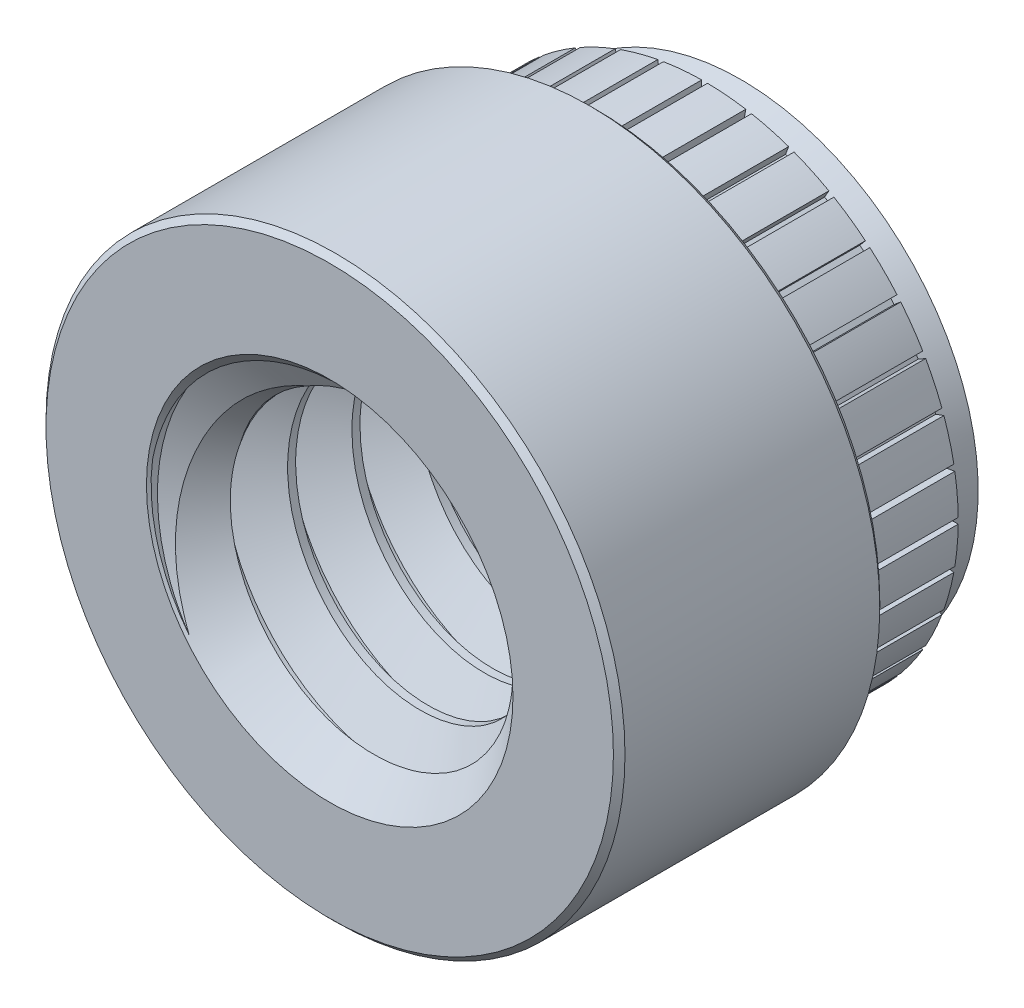
SolidWorks part; units mm, degrees
ref_plane "Front Plane" through (0, 0, 0) normal (0, 0, 1) x (1, 0, 0)
ref_plane "Top Plane" through (0, 0, 0) normal (0, 1, 0) x (1, 0, 0)
ref_plane "Right Plane" through (0, 0, 0) normal (1, 0, 0) x (0, 0, -1)
sketch "Sketch1" plane through (0, 0, 0) normal (0, 0, 1) x (1, 0, 0)
  circle A0 centre (0, 0) radius 6.35
  dimension "A" = 12.7
extrude "Extrude1" add sketch "Sketch1" against normal blind 5.842
sketch "Sketch15" plane through (0, 0, -5.842) normal (0, 0, -1) x (-1, 0, 0)
  circle A0 centre (0, 0) radius 5.2451
  dimension "hole dia" = 10.4902
sketch "Sketch2" plane through (0, 0, -5.842) normal (0, 0, -1) x (-1, 0, 0)
  circle A0 centre (0, 0) radius 5.5626
  dimension "D1" = 11.1252
extrude "Extrude2" add sketch "Sketch2" along normal blind 3.175
sketch "Sketch3" plane through (0, 0, -9.017) normal (0, 0, -1) x (-1, 0, 0)
  line L0 (0, 5.3721) -> (0, 6.35)
  circle A1 centre (0, 0) radius 6.35 construction
  circle A2 centre (0, 0) radius 5.3721
  circle A3 centre (0, 0) radius 5.3721 construction
  dimension "D1" = 0.1905
extrude "Cut-Extrude-Thin1" cut sketch "Sketch3" against normal up to surface (3.175 mm away) thin up to face at (6.35, 0, -5.842) thin type mid plane wall 0.127
pattern_circular "CirPattern1" count 36 over 360 about axis through (0, 0, 0) along (0, 0, 1) of "Cut-Extrude-Thin1"
sketch "Sketch5" plane through (0, 0, -9.017) normal (0, 0, -1) x (-1, 0, 0)
  circle A0 centre (0, 0) radius 6.35 construction
  circle A3 centre (0, 0) radius 5.207
  dimension "C" = 10.414
extrude "Cut-Extrude1" cut sketch "Sketch5" against normal blind 0.7937 draft 20 flip side to cut draft outward yes
chamfer "Chamfer2" distance 0.127 angle 45 2 edges at (6.35, 0, 0) (6.35, 0, -5.842)
sketch "Sketch7" plane through (0, 0, 0) normal (0, 0, 1) x (1, 0, 0)
  circle A0 centre (0, 0) radius 3.9688
  dimension "Thread Od" = 7.9375
extrude "Cut-Extrude3" cut sketch "Sketch7" against normal through all
sketch "Sketch8" plane through (0, 0, -9.017) normal (0, 0, -1) x (-1, 0, 0)
  circle A0 centre (0, 0) radius 3.9688 construction
  circle A1 centre (0, 0) radius 3.9688
curve "Helix/Spiral1" pitch 1.4111 height 12.192 turns 8.64 parameters "pitch"=1.4111
sketch "Sketch9" plane through (0, 0, 0) normal (1, 0, 0) x (0, 0, -1)
  line L0 (10.2517, 3.9688) -> (9.7226, 3.0522)
  line L1 (9.7226, 3.0522) -> (9.5462, 3.0522)
  line L2 (9.5462, 3.0522) -> (9.017, 3.9688)
  line L3 (10.2517, 3.9688) -> (9.017, 3.9688)
  line L4 (9.6344, 3.9688) -> (9.6344, 3.0522) construction
  line L5 (9.9871, 3.5105) -> (9.2816, 3.5105) construction
  line L6 (9.017, -3.9688) -> (9.017, 3.9688) construction
  dimension "D1" = 60
  dimension "D2" = 0.1764
  dimension "D3" = 0.7056
sweep "Sweep1" add profiles "Sketch9" path "Helix/Spiral1"
sketch "Sketch10" plane through (0, 0, 0) normal (0, 0, 1) x (1, 0, 0)
  circle A0 centre (0, 0) radius 6.35 construction
  circle A1 centre (0, 0) radius 6.35
extrude "Cut-Extrude4" cut sketch "Sketch10" along normal through all
sketch "Sketch11" plane through (0, 0, -9.017) normal (0, 0, -1) x (-1, 0, 0)
  circle A1 centre (0, 0) radius 5.207 construction
  circle A2 centre (0, 0) radius 5.207
extrude "Cut-Extrude5" cut sketch "Sketch11" along normal through all
sketch "Sketch13" plane through (0, 0, 0) normal (0, 0, 1) x (1, 0, 0)
  circle A2 centre (0, 0) radius 4.0196
  circle A3 centre (0, 0) radius 4.0196
  dimension "D1" = 0.0508
extrude "Cut-Extrude6" cut sketch "Sketch13" against normal through all draft 45
sketch "Sketch14" plane through (0, 0, -9.017) normal (0, 0, -1) x (-1, 0, 0)
  circle A2 centre (0, 0) radius 4.0196
  circle A3 centre (0, 0) radius 4.0196
  dimension "D1" = 0.0508
extrude "Cut-Extrude7" cut sketch "Sketch14" against normal through all draft 45
equation "\"D3@Helix/Spiral1\" = \"B@Extrude1\"+\"panel min.@Extrude2\"+.125"
equation "\"D2@Sketch9\" = \"pitch@Helix/Spiral1\"*.125"
equation "\"D3@Sketch9\" = \"pitch@Helix/Spiral1\"*.50"
equation "\"D1@Sketch2\" = \"hole dia@Sketch15\"+.025"
equation "\"D1@Cut-Extrude1\" = \"panel min.@Extrude2\"*.25"
